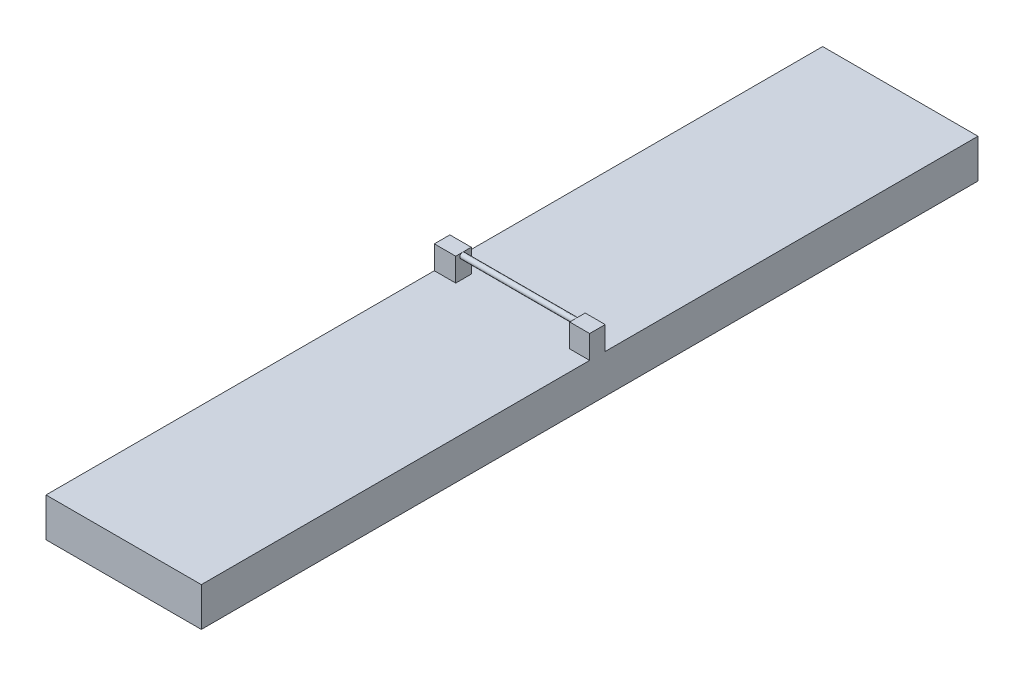
SolidWorks part; units mm, degrees
ref_plane "Plan de face" through (0, 0, 0) normal (0, 0, 1) x (1, 0, 0)
ref_plane "Plan de dessus" through (0, 0, 0) normal (0, 1, 0) x (1, 0, 0)
ref_plane "Plan de droite" through (0, 0, 0) normal (1, 0, 0) x (0, 0, -1)
sketch "Esquisse3" plane through (0, 0, 0) normal (1, 0, 0) x (0, 0, -1)
  line L1 (-50, 38.6) -> (950, 38.6)
  line L2 (-50, 38.6) -> (-50, -11.4)
  line L3 (-50, -11.4) -> (950, -11.4)
  line L4 (950, 38.6) -> (950, -11.4)
  line L5 (-50, 38.6) -> (950, -11.4) construction
  line L6 (-50, -11.4) -> (950, 38.6) construction
  point P0 (450, 13.6)
  dimension "D1" = 1000
  dimension "D2" = 50
extrude "Boss.-Extru.2" add sketch "Esquisse3" along normal blind 100 and the other way blind 100
sketch "Esquisse4" plane through (0, 38.6, 0) normal (0, 1, 0) x (1, 0, 0)
  line L0 (-100, 450) -> (104.6493, 450)
  line L1 (-100, 950) -> (-100, -50) construction
  line L2 (-100, 470) -> (100, 470)
  line L3 (100, 950) -> (100, -50) construction
  line L5 (-100, 450) -> (-72.4509, 450)
  line L6 (-100, 450) -> (-100, 470)
  line L7 (-100, 470) -> (-72.4509, 470)
  line L8 (-72.4509, 450) -> (-72.4509, 470)
  line L9 (100, 470) -> (74.2355, 470)
  line L10 (100, 470) -> (100, 450)
  line L11 (100, 450) -> (74.2355, 450)
  line L12 (74.2355, 470) -> (74.2355, 450)
  point P13 (100, 460)
  line M2 (100, -50) -> (100, 950)
  line M4 (-100, 950) -> (-100, -50)
  dimension "D1" = 10
  dimension "D2" = 20
extrude "Boss.-Extru.4" add sketch "Esquisse4" along normal blind 30 contours L0 L8 L2 M4 | L2 L12 L0 M2 region at (-86.2254, 38.6, -460) region at (87.1177, 38.6, -460)
sketch "Esquisse7" plane through (-72.4509, 0, 0) normal (1, 0, 0) x (0, 0, -1)
  circle A0 centre (458.6155, 65.1519) radius 3.4481
  point P0 (0, 0)
extrude "Boss.-Extru.5" add sketch "Esquisse7" along normal blind 157 and the other way blind 15
